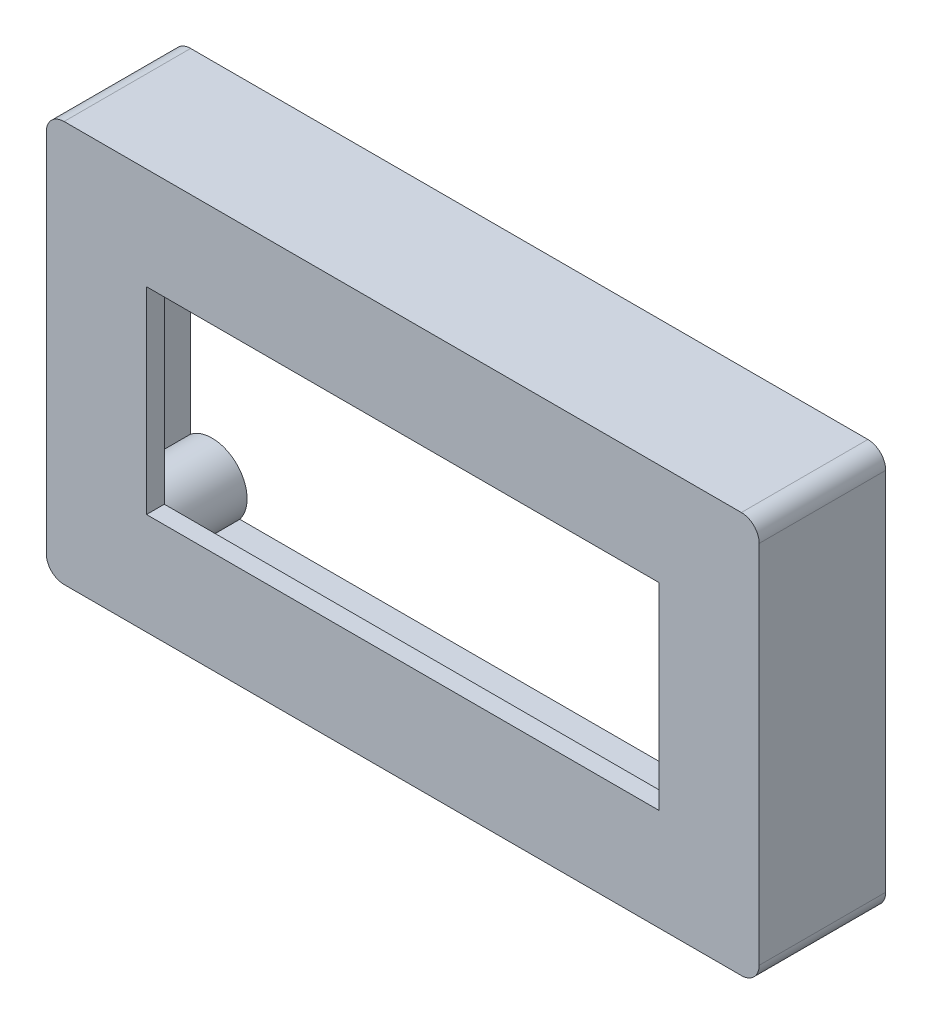
SolidWorks part; units mm, degrees
ref_plane "Front Plane" through (0, 0, 0) normal (0, 0, 1) x (1, 0, 0)
ref_plane "Top Plane" through (0, 0, 0) normal (0, 1, 0) x (1, 0, 0)
ref_plane "Right Plane" through (0, 0, 0) normal (1, 0, 0) x (0, 0, -1)
sketch "Sketch1" plane through (0, 0, 0) normal (0, 0, 1) x (1, 0, 0)
  line L0 (-48.26, 26.035) -> (-48.26, -26.035)
  line L1 (-50.8, 28.575) -> (50.8, 28.575)
  line L2 (-50.8, 28.575) -> (-50.8, -28.575)
  line L3 (-50.8, -28.575) -> (50.8, -28.575)
  line L4 (50.8, 28.575) -> (50.8, -28.575)
  line L5 (-48.26, -26.035) -> (48.26, -26.035)
  line L6 (48.26, 26.035) -> (48.26, -26.035)
  line L7 (-48.26, 26.035) -> (48.26, 26.035)
  dimension "D1" = 2.54
extrude "Boss-Extrude1" add sketch "Sketch1" along normal blind 15.494
sketch "Sketch2" plane through (0, 0, 15.494) normal (0, 0, 1) x (1, 0, 0)
  line L1 (-50.8, 28.575) -> (50.8, 28.575)
  line L2 (-50.8, 28.575) -> (-50.8, -28.575)
  line L3 (-50.8, -28.575) -> (50.8, -28.575)
  line L4 (50.8, 28.575) -> (50.8, -28.575)
  line L12 (35.4965, 13.0429) -> (-35.4965, 13.0429) construction
  line L13 (36.5125, -14.0589) -> (-36.5125, -14.0589)
  line L14 (36.5125, -14.0589) -> (36.5125, 14.0589)
  line L15 (36.5125, 14.0589) -> (-36.5125, 14.0589)
  line L16 (-36.5125, -14.0589) -> (-36.5125, 14.0589)
  line L17 (36.5125, -14.0589) -> (-36.5125, 14.0589) construction
  line L18 (36.5125, 14.0589) -> (-36.5125, -14.0589) construction
  line L19 (-35.4965, 13.0429) -> (-35.4965, -13.2715) construction
  point P6 (0, 0)
  dimension "D1" = 1.016
  dimension "D2" = 1.016
extrude "Boss-Extrude2" add sketch "Sketch2" along normal blind 2.54
sketch "Sketch3" plane through (0, 0, 15.494) normal (0, 0, -1) x (-1, 0, 0)
  line L0 (-50.8, 28.575) -> (-45.212, 22.987) construction
  line L1 (-48.26, 26.035) -> (48.26, 26.035) construction
  line L2 (0, 30.9999) -> (0, -6.7397) construction
  line L3 (-60.493, 0) -> (26.1789, 0) construction
  line L4 (-50.8, -26.035) -> (-50.8, 26.035) construction
  circle A0 centre (-45.212, 22.987) radius 5
  circle A1 centre (45.212, 22.987) radius 5
  circle A2 centre (45.212, -22.987) radius 5
  circle A3 centre (-45.212, -22.987) radius 5
  line M6 (48.26, -26.035) -> (48.26, 26.035)
  line M7 (48.26, 26.035) -> (-48.26, 26.035)
  line M8 (-48.26, 26.035) -> (-48.26, -26.035)
  line M9 (-48.26, -26.035) -> (48.26, -26.035)
  dimension "D2" = 10
  dimension "D1" = 45
  dimension "D3" = 5.588
extrude "Boss-Extrude3" add sketch "Sketch3" along normal up to surface (15.494 mm away) contours A0 M8 M7 | A0 M7 M8 | A1 M6 M7 | A1 M7 M6 | A3 M8 M9 | A3 M9 M8 | A2 region at (44.5155, 22.2905, 15.494) region at (44.7542, 26.1618, 15.494) region at (-44.5155, 22.2905, 15.494) region at (-46.7809, 27.6008, 15.494) region at (48.3868, -22.5292, 15.494) region at (44.5155, -22.2905, 15.494) up to face at (0, 0, 0)
sketch "Sketch4" plane through (0, 0, 0) normal (0, 0, -1) x (-1, 0, 0)
  circle A0 centre (-45.212, 22.987) radius 2.415
  circle A1 centre (45.212, -22.987) radius 2.415
  circle A2 centre (45.212, 22.987) radius 2.415
  circle A3 centre (-45.212, -22.987) radius 2.415
  point P8 (0, 0)
  point P11 (-45.212, -22.987)
  point P12 (-57.7576, -17.3982)
  point P13 (-45.212, -22.987)
  point P14 (0, 0)
  point P15 (45.212, 22.987)
  point P16 (0, 0)
  dimension "D1" = 4.83
extrude "Cut-Extrude1" cut sketch "Sketch4" against normal blind 6.35 contours A0 | A3 | A1 | A2 region at (45.212, 22.987, 0) region at (-45.212, -22.987, 0) region at (-45.212, 22.987, 0) region at (45.212, -22.987, 0)
sketch "Sketch5" plane through (0, 0, 6.35) normal (0, 0, -1) x (-1, 0, 0)
  circle A0 centre (-45.212, 22.987) radius 1.5
  circle A1 centre (45.212, 22.987) radius 1.5
  circle A2 centre (45.212, -22.987) radius 1.5
  circle A3 centre (-45.212, -22.987) radius 1.5
  point P5 (-45.212, -22.987)
  point P12 (45.212, 22.987)
  dimension "D1" = 3
extrude "Cut-Extrude2" cut sketch "Sketch5" against normal offset from surface (7.874 mm away) 1.27 contours A0 | A2 | A3 | A1 region at (45.212, 22.987, 6.35) up to face at (0, 0, 15.494)
ref_axis "Axis1" through (45.212, 22.987, 6.35) along (0, 0, -1)
ref_plane "Plane1" through (0, 22.987, 0) normal (0, -1, 0) x (0, 0, -1)
ref_axis "Axis2" through (-45.212, -22.987, 6.35) along (0, 0, -1)
ref_plane "Plane2" through (0, -22.987, 0) normal (0, 1, 0) x (0, 0, -1)
ref_axis "Axis3" through (45.212, -22.987, 6.35) along (0, 0, -1)
ref_plane "Plane3" through (0, -22.987, 0) normal (0, -1, 0) x (0, 0, -1)
ref_axis "Axis4" through (-45.212, 22.987, 6.35) along (0, 0, -1)
ref_plane "Plane4" through (0, 22.987, 0) normal (0, 1, 0) x (0, 0, -1)
sketch "Sketch6" plane through (0, 22.987, 0) normal (0, -1, 0) x (0, 0, -1)
  line L0 (0, 48.012) -> (-6.35, 46.8923)
  line L1 (0, -50.8) -> (0, 50.8) construction
  line L2 (-6.35, 42.797) -> (-6.35, 47.627) construction
  line L3 (-6.35, 46.8923) -> (-6.35, 45.212)
  line L4 (-6.35, 43.712) -> (-6.35, 46.712) construction
  line L5 (-6.35, 45.212) -> (0, 45.212)
  line L6 (-6.35, 45.212) -> (0, 45.212) construction
  line L7 (0, 45.212) -> (0, 48.012)
  dimension "D1" = 2.8
  dimension "D2" = 80
revolve "Cut-Revolve1" cut sketch "Sketch6" angle 360 about L5
sketch "Sketch7" plane through (0, -22.987, 0) normal (0, 1, 0) x (0, 0, -1)
  line L7 (0, 48.006) -> (-6.35, 46.8863)
  line L8 (0, 40.212) -> (0, 48.26) construction
  line L9 (-6.35, 42.797) -> (-6.35, 47.627) construction
  line L10 (-6.35, 46.8863) -> (-6.35, 45.212)
  line L11 (-6.35, 45.212) -> (0, 45.212)
  line L12 (0, 45.212) -> (0, 48.006)
  dimension "D1" = 80
  dimension "D2" = 2.794
revolve "Cut-Revolve2" cut sketch "Sketch7" angle 360 about L11
sketch "Sketch8" plane through (0, 22.987, 0) normal (0, 1, 0) x (0, 0, -1)
  line L0 (0, 48.006) -> (-6.35, 46.8863)
  line L1 (0, -50.8) -> (0, 50.8) construction
  line L2 (-6.35, 42.797) -> (-6.35, 47.627) construction
  line L3 (-6.35, 46.8863) -> (-6.35, 45.212)
  line L4 (-6.35, 45.212) -> (3.0728, 45.212) construction
  line L5 (0, 48.006) -> (0, 45.212)
  line L6 (-6.35, 45.212) -> (0, 45.212)
  dimension "D1" = 80
  dimension "D2" = 2.794
sketch "Sketch9" plane through (0, -22.987, 0) normal (0, -1, 0) x (0, 0, -1)
  line L0 (0, 48.006) -> (-6.35, 46.8863)
  line L1 (0, -50.8) -> (0, 50.8) construction
  line L2 (-6.35, 42.797) -> (-6.35, 47.627) construction
  line L3 (-6.35, 46.8863) -> (-6.35, 45.212)
  line L4 (-6.35, 45.212) -> (0, 45.212)
  line L5 (0, 45.212) -> (0, 48.006)
  dimension "D1" = 80
  dimension "D2" = 2.794
revolve "Cut-Revolve3" cut sketch "Sketch8" angle 360 about L4
revolve "Cut-Revolve4" cut sketch "Sketch9" angle 360 about axis through (45.212, -22.987, 6.35) along (0, 0, -1)
fillet "Fillet1" radius 2.54 4 edges at (50.8, -28.575, 9.017) (50.8, 28.575, 9.017) (-50.8, 28.575, 9.017) (-50.8, -28.575, 9.017)
